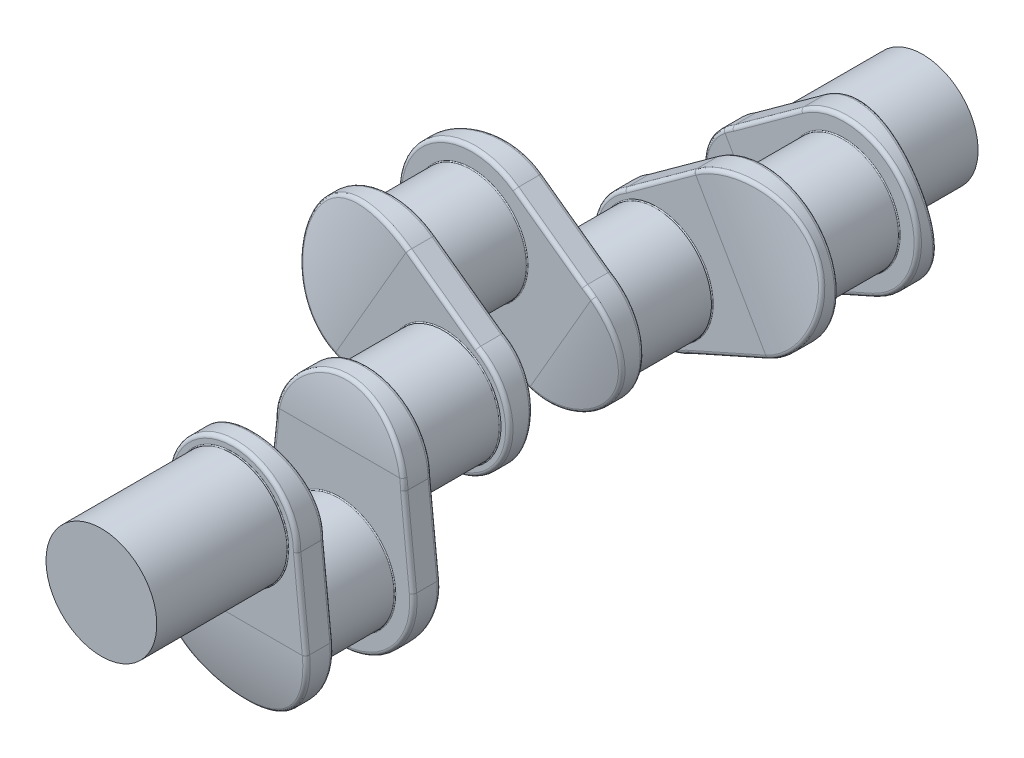
SolidWorks part; units mm, degrees
ref_plane "Front Plane" through (0, 0, 0) normal (0, 0, 1) x (1, 0, 0)
ref_plane "Top Plane" through (0, 0, 0) normal (0, 1, 0) x (1, 0, 0)
ref_plane "Right Plane" through (0, 0, 0) normal (1, 0, 0) x (0, 0, -1)
sketch "Sketch1" plane through (0, 0, 0) normal (0, 0, 1) x (1, 0, 0)
  circle A0 centre (0, 0) radius 38.1
  dimension "D1" = 76.2
extrude "Boss-Extrude1" add sketch "Sketch1" along normal blind 27.31
sketch "Sketch2" plane through (0, 0, 27.31) normal (0, 0, 1) x (1, 0, 0)
  line L0 (-44.45, 63.5) -> (-50.5257, 5.272)
  line L1 (44.45, 63.5) -> (50.5257, 5.272)
  arc A0 (-50.5257, 5.272) -> (50.5257, 5.272) centre (0, 0) ccw
  arc A1 (44.45, 63.5) -> (-44.45, 63.5) centre (0, 63.5) ccw
  circle A2 centre (0, 0) radius 38.1 construction
  dimension "D1" = 12.7
  dimension "D2" = 88.9
  dimension "D3" = 63.5
extrude "Boss-Extrude2" add sketch "Sketch2" along normal blind 19
sketch "Sketch3" plane through (0, 0, 46.31) normal (0, 0, 1) x (1, 0, 0)
  circle A0 centre (0, 63.5) radius 38.1
  dimension "D1" = 76.2
extrude "Boss-Extrude3" add sketch "Sketch3" along normal blind 26.67
sketch "Sketch4" plane through (0, 0, 0) normal (1, 0, 0) x (0, 0, -1)
  line L0 (-46.31, -50.8) -> (-27.31, -50.8) construction
  line L1 (-46.31, 5.272) -> (-55.6699, 5.272)
  line L2 (-55.6699, 5.272) -> (-55.6699, -50.8)
  line L3 (-55.6699, -50.8) -> (-36.81, -50.8)
  arc A0 (-46.31, 5.272) -> (-36.81, -50.8) centre (122.6899, 5.064) ccw
  dimension "D1" = 169
extrude "Cut-Extrude1" cut sketch "Sketch4" against normal through all both and the other way through all
sketch "Sketch5" plane through (0, 0, 0) normal (1, 0, 0) x (0, 0, -1)
  line L0 (-27.31, 107.95) -> (-46.31, 107.95) construction
  line L1 (-27.31, 63.5) -> (-27.31, 107.95) construction
  line L2 (-32.31, 107.95) -> (-21.8046, 107.95)
  line L3 (-21.8046, 107.95) -> (-21.8046, 63.5)
  line L4 (-21.8046, 63.5) -> (-27.31, 63.5)
  arc A0 (-27.31, 63.5) -> (-32.31, 107.95) centre (-196.2738, 67.0002) ccw
  dimension "D2" = 169
  dimension "D1" = 5
extrude "Cut-Extrude2" cut sketch "Sketch5" against normal through all both and the other way through all
fillet "Fillet1" radius 2.54 10 edges at (-47.4878, 34.386, 27.31) (0, -50.8, 27.31) (-47.4878, 34.386, 46.31) (-50.547, 5.0641, 46.31) (0.0331, -50.8, 36.81) (50.547, 5.0641, 46.31) (3.1078, 107.8412, 32.2829) (47.4878, 34.386, 27.31) (0, 107.95, 46.31) (47.4878, 34.386, 46.31)
fillet "Fillet2" radius 0.64 2 edges at (38.1, 0, 27.31) (38.1, 63.5, 46.31)
mirror "Mirror1" about plane through (0, 0, 0) normal (0, 0, 1) of bodies 105
ref_axis "Axis1" through (0, 63.5, 264.1635) along (0, 0, -1)
pattern_linear "LPattern1" count 3 spacing 145.96 along (0, 0, -1) of bodies 106
move or copy body "Body-Move/Copy1" bodies to move or copy 107 copy no rotation origin (0, 63.5, 0) rotation axis (0, 0, -1) rotation angle 120
move or copy body "Body-Move/Copy2" bodies to move or copy 108 copy no rotation origin (0, 63.5, 0) rotation axis (0, 0, 1) rotation angle 120
sketch "Sketch6" plane through (0, 0, 72.98) normal (0, 0, 1) x (1, 0, 0)
  circle A1 centre (0, 63.5) radius 38.1
  circle A2 centre (0, 63.5) radius 38.1
  dimension "D1" = 0
extrude "Boss-Extrude4" add sketch "Sketch6" along normal blind 63.5
sketch "Sketch7" plane through (0, 0, -364.9) normal (0, 0, -1) x (-1, 0, 0)
  circle A1 centre (0, 63.5) radius 38.1
  circle A2 centre (0, 63.5) radius 38.1
  dimension "D1" = 0
extrude "Boss-Extrude5" add sketch "Sketch7" along normal blind 63.5
combine bodies "Combine1" operation type add bodies to combine 111 109 112
